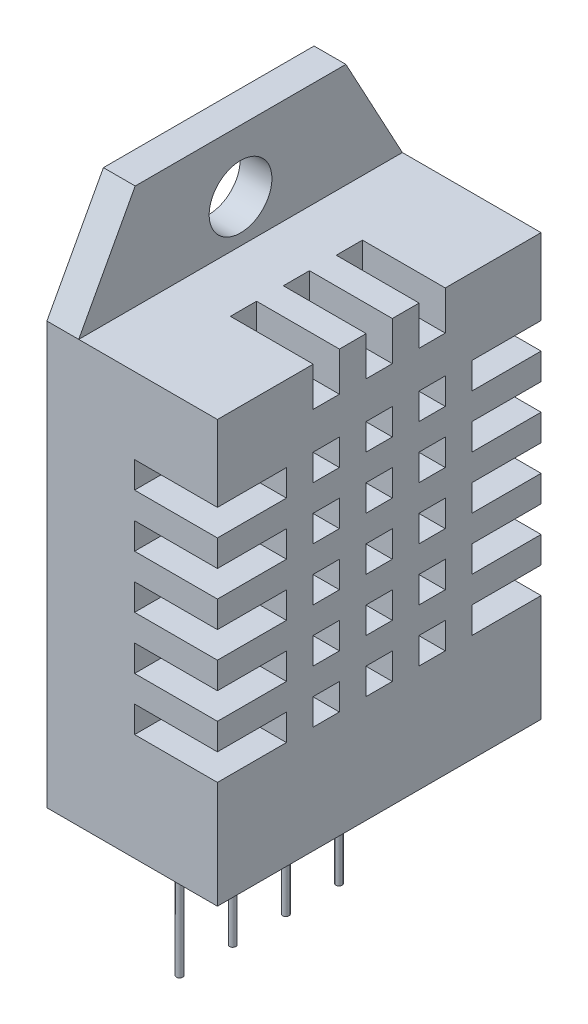
SolidWorks part; units mm, degrees
ref_plane "Front Plane" through (0, 0, 0) normal (0, 0, 1) x (1, 0, 0)
ref_plane "Top Plane" through (0, 0, 0) normal (0, 1, 0) x (1, 0, 0)
ref_plane "Right Plane" through (0, 0, 0) normal (1, 0, 0) x (0, 0, -1)
sketch "Sketch1" plane through (0, 0, 0) normal (1, 0, 0) x (0, 0, -1)
  line L0 (-7.735, 7.575) -> (7.735, 7.575)
  line L1 (-5.035, 12.575) -> (5.035, 12.575)
  line L2 (-7.735, 7.575) -> (-7.735, -12.575)
  line L3 (-7.735, -12.575) -> (7.735, -12.575)
  line L4 (7.735, 7.575) -> (7.735, -12.575)
  line L5 (-6.2972, 10.2376) -> (7.735, -12.575) construction
  line L6 (-7.735, -12.575) -> (6.2972, 10.2376) construction
  line L7 (5.035, 12.575) -> (7.735, 7.575)
  line L8 (0, 12.575) -> (0, -12.575) construction
  line L9 (-5.035, 12.575) -> (-7.735, 7.575)
  circle A0 centre (0, 9.615) radius 1.5
  point P0 (0, 0)
  point P14 (0, 11.115)
  dimension "D1" = 1.46
  dimension "D3" = 5
extrude "Boss-Extrude1" add sketch "Sketch1" along normal blind 8.15 contours L4 L0 L2 L3 region at (0, -2.5, 0)
extrude "Boss-Extrude2" add sketch "Sketch1<4>" along normal blind 1.52 contours L1 L9 L0 L7 region at (0, 9.9978, 6.2419)
sketch "Sketch1<4>" plane through (0, 0, 0) normal (1, 0, 0) x (0, 0, -1) same geometry as "Sketch1"
shell "Shell1" thickness 1.28
sketch "Sketch2" plane through (8.15, 0, 0) normal (1, 0, 0) x (0, 0, -1)
  line L0 (-7.735, 7.575) -> (7.735, 7.575) construction
  line L1 (3.155, 7.575) -> (3.155, 5.705)
  line L2 (-0.625, 7.575) -> (-0.625, 5.705)
  line L3 (-0.625, 5.705) -> (0.625, 5.705)
  line L4 (0.625, 7.575) -> (0.625, 5.705)
  line L5 (0, 7.575) -> (0.625, 5.705) construction
  line L6 (-0.625, 5.705) -> (0, 7.575) construction
  line L7 (1.905, 5.705) -> (3.155, 5.705)
  line L8 (-0.625, 7.575) -> (0.625, 7.575)
  line L9 (1.905, 7.575) -> (1.905, 5.705)
  line L10 (1.905, 7.575) -> (3.155, 7.575)
  line L11 (2.53, 7.575) -> (3.155, 5.705) construction
  line L12 (1.905, 5.705) -> (2.53, 7.575) construction
  line L13 (-1.905, 7.575) -> (-1.905, 5.705)
  line L14 (-3.155, 5.705) -> (-1.905, 5.705)
  line L15 (-3.155, 7.575) -> (-1.905, 7.575)
  line L16 (-2.53, 7.575) -> (-1.905, 5.705) construction
  line L17 (-3.155, 7.575) -> (-3.155, 5.705)
  line L18 (-3.155, 5.705) -> (-2.53, 7.575) construction
  line L19 (-0.625, 3.935) -> (0.625, 3.935)
  line L20 (-3.155, 2.6708) -> (-1.905, 2.6708)
  line L21 (-3.155, 2.6708) -> (-3.155, 3.935)
  line L22 (-3.155, 3.935) -> (-1.905, 3.935)
  line L23 (-1.905, 2.6708) -> (-1.905, 3.935)
  line L24 (-3.155, 2.6708) -> (-1.905, 3.935) construction
  line L25 (-3.155, 3.935) -> (-1.905, 2.6708) construction
  line L26 (-0.625, 2.6708) -> (-0.625, 3.935)
  line L27 (0.625, 2.6708) -> (0.625, 3.935)
  line L28 (-0.625, 2.6708) -> (0.625, 2.6708)
  line L29 (1.905, 3.935) -> (3.155, 3.935)
  line L30 (1.905, 2.6708) -> (1.905, 3.935)
  line L31 (3.155, 2.6708) -> (3.155, 3.935)
  line L32 (1.905, 2.6708) -> (3.155, 2.6708)
  line L33 (-0.625, 1.405) -> (0.625, 1.405)
  line L34 (-0.625, 0.1408) -> (-0.625, 1.405)
  line L35 (0.625, 0.1408) -> (0.625, 1.405)
  line L36 (-0.625, 0.1408) -> (0.625, 0.1408)
  line L37 (1.905, 1.405) -> (3.155, 1.405)
  line L38 (1.905, 0.1408) -> (1.905, 1.405)
  line L39 (3.155, 0.1408) -> (3.155, 1.405)
  line L40 (1.905, 0.1408) -> (3.155, 0.1408)
  line L41 (-0.625, -1.125) -> (0.625, -1.125)
  line L42 (-0.625, -2.3892) -> (-0.625, -1.125)
  line L43 (0.625, -2.3892) -> (0.625, -1.125)
  line L44 (-0.625, -2.3892) -> (0.625, -2.3892)
  line L45 (1.905, -1.125) -> (3.155, -1.125)
  line L46 (1.905, -2.3892) -> (1.905, -1.125)
  line L47 (3.155, -2.3892) -> (3.155, -1.125)
  line L48 (1.905, -2.3892) -> (3.155, -2.3892)
  line L49 (-0.625, -3.655) -> (0.625, -3.655)
  line L50 (-0.625, -4.9192) -> (-0.625, -3.655)
  line L51 (0.625, -4.9192) -> (0.625, -3.655)
  line L52 (-0.625, -4.9192) -> (0.625, -4.9192)
  line L53 (1.905, -3.655) -> (3.155, -3.655)
  line L54 (1.905, -4.9192) -> (1.905, -3.655)
  line L55 (3.155, -4.9192) -> (3.155, -3.655)
  line L56 (1.905, -4.9192) -> (3.155, -4.9192)
  line L57 (-0.625, -6.185) -> (0.625, -6.185)
  line L58 (-0.625, -7.4492) -> (-0.625, -6.185)
  line L59 (0.625, -7.4492) -> (0.625, -6.185)
  line L60 (-0.625, -7.4492) -> (0.625, -7.4492)
  line L61 (1.905, -6.185) -> (3.155, -6.185)
  line L62 (1.905, -7.4492) -> (1.905, -6.185)
  line L63 (3.155, -7.4492) -> (3.155, -6.185)
  line L64 (1.905, -7.4492) -> (3.155, -7.4492)
  line L65 (-3.155, 1.405) -> (-1.905, 1.405)
  line L66 (-3.155, 0.1408) -> (-3.155, 1.405)
  line L67 (-1.905, 0.1408) -> (-1.905, 1.405)
  line L68 (-3.155, 0.1408) -> (-1.905, 0.1408)
  line L69 (-3.155, -1.125) -> (-1.905, -1.125)
  line L70 (-3.155, -2.3892) -> (-3.155, -1.125)
  line L71 (-1.905, -2.3892) -> (-1.905, -1.125)
  line L72 (-3.155, -2.3892) -> (-1.905, -2.3892)
  line L73 (-3.155, -3.655) -> (-1.905, -3.655)
  line L74 (-3.155, -4.9192) -> (-3.155, -3.655)
  line L75 (-1.905, -4.9192) -> (-1.905, -3.655)
  line L76 (-3.155, -4.9192) -> (-1.905, -4.9192)
  line L77 (-3.155, -6.185) -> (-1.905, -6.185)
  line L78 (-3.155, -7.4492) -> (-3.155, -6.185)
  line L79 (-1.905, -7.4492) -> (-1.905, -6.185)
  line L80 (-3.155, -7.4492) -> (-1.905, -7.4492)
  line L81 (-7.7805, 2.6708) -> (-4.435, 3.935) construction
  line L82 (-7.7805, 2.6708) -> (-7.7805, 3.935)
  line L83 (-7.7805, 3.935) -> (-4.435, 2.6708) construction
  line L84 (-7.7805, 3.935) -> (-4.435, 3.935)
  line L85 (-4.435, 2.6708) -> (-4.435, 3.935)
  line L86 (-7.7805, 2.6708) -> (-4.435, 2.6708)
  line L87 (0, 12.575) -> (0, -10.4162) construction
  line L88 (-5.035, 12.575) -> (5.035, 12.575) construction
  line L89 (0, 12.575) -> (0, -12.575) construction
  line L90 (7.7805, 3.935) -> (4.435, 2.6708) construction
  line L91 (7.7805, 2.6708) -> (4.435, 3.935) construction
  line L92 (7.7805, 2.6708) -> (4.435, 2.6708)
  line L93 (4.435, 2.6708) -> (4.435, 3.935)
  line L94 (7.7805, 3.935) -> (4.435, 3.935)
  line L95 (7.7805, 2.6708) -> (7.7805, 3.935)
  line L96 (-7.7805, 1.405) -> (-4.435, 1.405)
  line L97 (-4.435, 0.1408) -> (-4.435, 1.405)
  line L98 (-7.7805, 0.1408) -> (-4.435, 0.1408)
  line L99 (-7.7805, 0.1408) -> (-7.7805, 1.405)
  line L100 (7.7805, 0.1408) -> (4.435, 0.1408)
  line L101 (4.435, 0.1408) -> (4.435, 1.405)
  line L102 (7.7805, 1.405) -> (4.435, 1.405)
  line L103 (7.7805, 0.1408) -> (7.7805, 1.405)
  line L104 (-7.7805, -1.125) -> (-4.435, -1.125)
  line L105 (-4.435, -2.3892) -> (-4.435, -1.125)
  line L106 (-7.7805, -2.3892) -> (-4.435, -2.3892)
  line L107 (-7.7805, -2.3892) -> (-7.7805, -1.125)
  line L108 (7.7805, -2.3892) -> (4.435, -2.3892)
  line L109 (4.435, -2.3892) -> (4.435, -1.125)
  line L110 (7.7805, -1.125) -> (4.435, -1.125)
  line L111 (7.7805, -2.3892) -> (7.7805, -1.125)
  line L112 (-7.7805, -3.655) -> (-4.435, -3.655)
  line L113 (-4.435, -4.9192) -> (-4.435, -3.655)
  line L114 (-7.7805, -4.9192) -> (-4.435, -4.9192)
  line L115 (-7.7805, -4.9192) -> (-7.7805, -3.655)
  line L116 (7.7805, -4.9192) -> (4.435, -4.9192)
  line L117 (4.435, -4.9192) -> (4.435, -3.655)
  line L118 (7.7805, -3.655) -> (4.435, -3.655)
  line L119 (7.7805, -4.9192) -> (7.7805, -3.655)
  line L120 (-7.7805, -6.185) -> (-4.435, -6.185)
  line L121 (-4.435, -7.4492) -> (-4.435, -6.185)
  line L122 (-7.7805, -7.4492) -> (-4.435, -7.4492)
  line L123 (-7.7805, -7.4492) -> (-7.7805, -6.185)
  line L124 (7.7805, -7.4492) -> (4.435, -7.4492)
  line L125 (4.435, -7.4492) -> (4.435, -6.185)
  line L126 (7.7805, -6.185) -> (4.435, -6.185)
  line L127 (7.7805, -7.4492) -> (7.7805, -6.185)
  point P0 (0, 7.575)
  point P2 (2.53, 7.575)
  point P14 (-2.53, 7.575)
  point P20 (-2.53, 4.043)
  point P25 (-5.06, 4.043)
  point P96 (5.06, 4.043)
  line M66 (7.735, -12.575) -> (7.735, 7.575)
  line M67 (7.735, 7.575) -> (-7.735, 7.575)
  line M68 (-7.735, 7.575) -> (-7.735, -12.575)
  dimension "D1" = 1.25
  dimension "D2" = 1.25
  dimension "D3" = 1.77
  dimension "D4" = 3
  dimension "D5" = 5
  dimension "D6" = 5
extrude "Cut-Extrude1" cut sketch "Sketch2" against normal blind 3.96 contours L4 L2 L3 M67 | L9 L7 L1 M67 | L38 L40 L39 L37 | L102 L101 L100 M66 | L94 L93 L92 M66 | L26 L28 L27 L19 | L66 L68 L67 L65 | L20 L23 L22 L21 | L86 L85 L84 M68 | L98 L97 L96 M68 | L106 L105 L104 M68 | L114 L113 L112 M68 | L70 L72 L71 L69 | L42 L44 L43 L41 | L46 L48 L47 L45 | L110 L109 L108 M66 | L118 L117 L116 M66 | L54 L56 L55 L53 | L50 L52 L51 L49 | L74 L76 L75 L73 | L126 L125 L124 M66 | L62 L64 L63 L61 | L78 L80 L79 L77 | L122 L121 L120 M68 | L14 L13 L15 L17 | L31 L29 L30 L32 | L35 L33 L34 L36 | L59 L57 L58 L60 region at (8.15, -6.8171, 6.085) region at (8.15, -4.2871, 6.085) region at (8.15, -1.7571, 6.085) region at (8.15, 0.7729, 6.085) region at (8.15, 3.3029, 6.085) region at (8.15, 6.64, 0) region at (8.15, 6.64, -2.53) region at (8.15, -6.8171, -6.085) region at (8.15, -4.2871, -6.085) region at (8.15, -1.7571, -6.085) region at (8.15, 0.7729, -6.085) region at (8.15, 3.3029, -6.085) region at (8.15, 3.3029, 0) region at (8.15, 3.3029, 2.53) region at (8.15, 0.7729, -2.53) region at (8.15, -1.7571, 0) region at (8.15, -1.7571, -2.53) region at (8.15, -4.2871, 0) region at (8.15, -4.2871, -2.53) region at (8.15, -6.8171, -2.53) region at (8.15, 0.7729, 2.53) region at (8.15, -1.7571, 2.53) region at (8.15, -4.2871, 2.53) region at (8.15, -6.8171, 2.53)
sketch "Sketch3" plane through (0, -12.575, 0) normal (0, -1, 0) x (1, 0, 0)
  line L0 (2.31, 7.735) -> (2.31, -7.735) construction
  line L1 (8.15, 7.735) -> (0, 7.735) construction
  line L2 (8.15, -7.735) -> (0, -7.735) construction
  line L3 (0, 5.035) -> (0, 7.735) construction
  circle A0 centre (2.31, 3.7043) radius 0.15
  circle A1 centre (2.31, 1.1643) radius 0.15
  circle A2 centre (2.31, -1.3757) radius 0.15
  circle A3 centre (2.31, -3.9157) radius 0.15
  dimension "D2" = 4
  dimension "D1" = 2.31
extrude "Boss-Extrude3" add sketch "Sketch3" along normal blind 7.8
